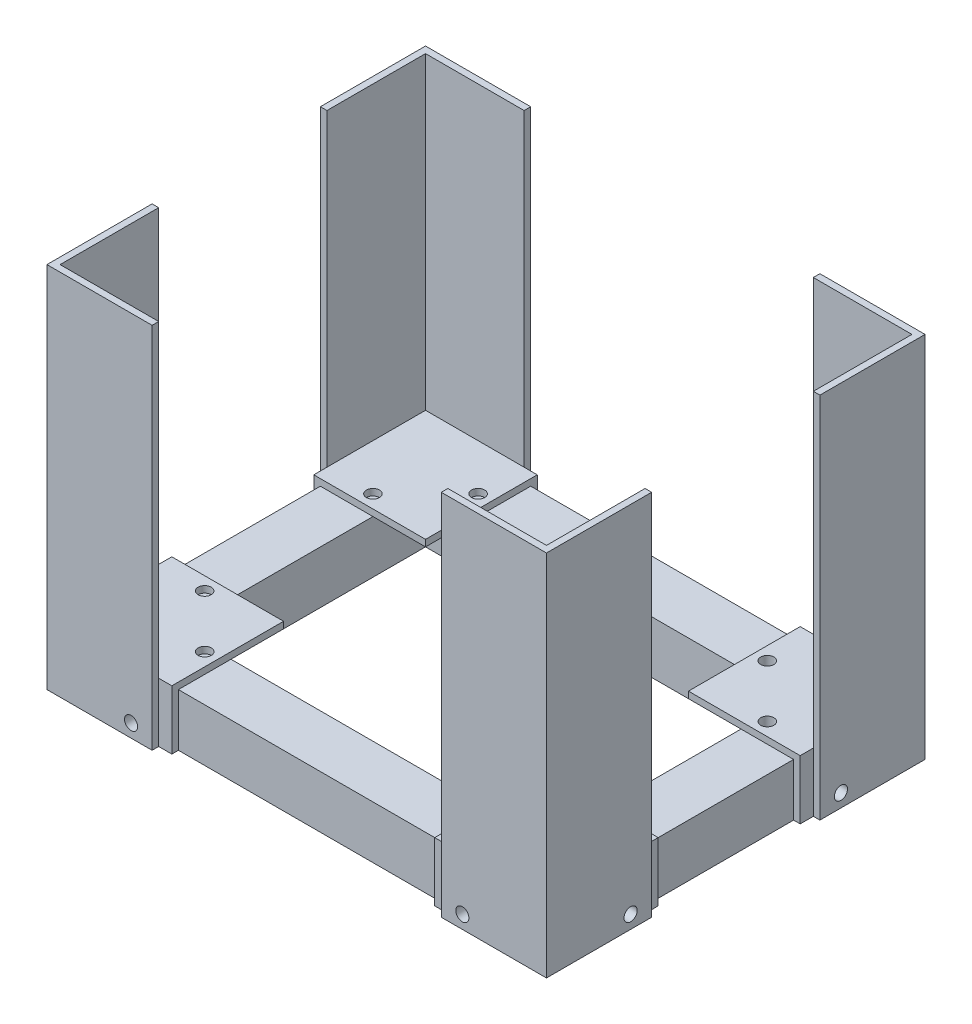
SolidWorks part; units mm, degrees
ref_plane "Front Plane" through (0, 0, 0) normal (0, 0, 1) x (1, 0, 0)
ref_plane "Top Plane" through (0, 0, 0) normal (0, 1, 0) x (1, 0, 0)
ref_plane "Right Plane" through (0, 0, 0) normal (1, 0, 0) x (0, 0, -1)
sketch "Sketch2" plane through (0, 0, 0) normal (0, 1, 0) x (1, 0, 0)
  line L0 (88.9, -59.69) -> (114.3, -59.69)
  line L1 (114.3, 85.09) -> (-114.3, 85.09)
  line L2 (114.3, 85.09) -> (114.3, -85.09)
  line L3 (114.3, -85.09) -> (-114.3, -85.09)
  line L4 (-114.3, 85.09) -> (-114.3, -85.09)
  line L5 (0, -85.09) -> (0, 85.09) construction
  line L6 (114.3, 0) -> (-114.3, 0) construction
  line L7 (-88.9, 59.69) -> (88.9, 59.69)
  line L8 (-88.9, 59.69) -> (-88.9, -59.69)
  line L9 (-88.9, -59.69) -> (88.9, -59.69)
  line L10 (88.9, 59.69) -> (88.9, -59.69)
  line L11 (0, -59.69) -> (0, 59.69) construction
  line L12 (-88.9, 0) -> (88.9, 0) construction
  line L13 (114.3, -59.69) -> (88.9, -59.69)
  line L14 (-114.3, -59.69) -> (-88.9, -59.69)
  line L17 (-88.9, 59.69) -> (-114.3, 59.69)
  line L18 (-114.3, 59.69) -> (-88.9, 59.69)
  line L19 (88.9, 59.69) -> (114.3, 59.69)
  line L20 (114.3, 59.69) -> (88.9, 59.69)
  point P0 (0, 0)
  point P4 (0, 0)
  dimension "D1" = 228.6
  dimension "D2" = 170.18
  dimension "D3" = 177.8
  dimension "D4" = 119.38
extrude "Boss-Extrude1" add sketch "Sketch2" along normal blind 25.4 contours L14 L4 L3 L2 L0 L9 | L19 L10 L0 L2 | L7 L19 L2 L1 L4 L17 | L8 L17 L4 L14 region at (101.6, 0, 0) region at (0, 0, 72.39) region at (-101.6, 0, 0) region at (0, 0, -72.39)
sketch "Sketch8" plane through (0, 25.4, 0) normal (0, 1, 0) x (1, 0, 0)
  line L1 (-114.3, -85.09) -> (-63.5, -85.09)
  line L2 (-114.3, -85.09) -> (-114.3, -88.265)
  line L3 (-114.3, -88.265) -> (-63.5, -88.265)
  line L4 (-63.5, -85.09) -> (-63.5, -88.265)
  line L5 (-114.3, -88.265) -> (-117.475, -88.265)
  line L6 (-114.3, -88.265) -> (-114.3, -34.29)
  line L7 (-114.3, -34.29) -> (-117.475, -34.29)
  line L8 (-117.475, -88.265) -> (-117.475, -34.29)
  dimension "D1" = 50.8
  dimension "D2" = 53.975
  dimension "D3" = 3.175
  dimension "D4" = 3.175
extrude "Boss-Extrude9" add sketch "Sketch8" against normal blind 25.4 contours L2 L1 L4 L3 | L6 L7 L8 L5
sketch "Sketch11" plane through (0, 25.4, 0) normal (0, 1, 0) x (1, 0, 0)
  line L0 (-117.475, -88.265) -> (-63.5, -88.265)
  line L1 (-117.475, -88.265) -> (-117.475, -34.29)
  line L2 (-63.5, -88.265) -> (-63.5, -34.29)
  line L3 (-117.475, -34.29) -> (-63.5, -34.29)
  point P0 (-196.4741, 4.7858)
extrude "Boss-Extrude12" add sketch "Sketch11" along normal blind 3.175
chamfer "Chamfer3" distance 5.08 angle 45 1 edges at (-117.475, 14.2875, 88.265)
sketch "Sketch10" plane through (0, 0, 0) normal (0, -1, 0) x (-1, 0, 0)
  line L0 (112.395, -88.265) -> (63.5, -88.265) construction
  line L1 (117.475, -83.185) -> (117.475, -34.29) construction
  line L2 (117.475, -40.64) -> (120.65, -40.64)
  line L3 (117.475, -40.64) -> (117.475, -88.265)
  line L4 (117.475, -88.265) -> (120.65, -88.265)
  line L5 (120.65, -40.64) -> (120.65, -88.265)
  line L7 (120.65, -88.265) -> (69.85, -88.265)
  line L8 (120.65, -88.265) -> (120.65, -91.44)
  line L9 (120.65, -91.44) -> (69.85, -91.44)
  line L10 (69.85, -88.265) -> (69.85, -91.44)
  point P4 (0, 0)
  point P5 (117.7066, -89.4721)
  point P10 (0, 0)
  point P12 (0, 0)
  point P13 (0, 0)
  point P14 (0, 0)
  point P15 (0, 0)
  point P16 (117.1952, -92.4558)
  dimension "D1" = 50.8
  dimension "D2" = 3.175
  dimension "D3" = 47.625
  dimension "D4" = 3.175
  dimension "D5" = 0
  dimension "D6" = 0
extrude "Boss-Extrude11" add sketch "Sketch10" against normal blind 177.8 contours L5 L2 L3 L4 | L8 L9 L10 L7
sketch "Sketch13" plane through (0, 0, 91.44) normal (0, 0, 1) x (1, 0, 0)
  line L0 (-69.85, 177.8) -> (-69.85, 0) construction
  line L1 (-120.65, 0) -> (-69.85, 0) construction
  circle A0 centre (-80.01, 6.35) radius 3.175
  dimension "D1" = 6.35
  dimension "D2" = 10.16
  dimension "D3" = 6.35
extrude "Cut-Extrude3" cut sketch "Sketch13" against normal blind 31.75
sketch "Sketch14" plane through (0, 28.575, 0) normal (0, 1, 0) x (1, 0, 0)
  line L1 (-63.5, -85.09) -> (-63.5, -59.69) construction
  line L2 (-63.5, -59.69) -> (88.9, -59.69) construction
  line L3 (-63.5, -34.29) -> (-117.475, -34.29) construction
  line L5 (-88.9, 59.69) -> (-88.9, -34.29) construction
  circle A0 centre (-69.85, -66.04) radius 3.175
  circle A1 centre (-95.25, -40.64) radius 3.175
  point P12 (-92.7177, -34.29)
  point P13 (-117.475, -38.1119)
  point P14 (0, 0)
  point P15 (0, 0)
  dimension "D1" = 6.35
  dimension "D3" = 6.35
  dimension "D4" = 6.35
  dimension "D2" = 6.35
  dimension "D5" = 6.35
  dimension "D6" = 6.35
extrude "Cut-Extrude4" cut sketch "Sketch14" against normal up to surface (28.575 mm away) up to face at (-61.9125, 0, 42.4392)
sketch "Sketch16" plane through (-120.65, 0, 0) normal (-1, 0, 0) x (0, 0, 1)
  line L0 (40.64, 0) -> (91.44, 0) construction
  line L1 (40.64, 177.8) -> (40.64, 0) construction
  circle A0 centre (50.8, 6.35) radius 3.175
  dimension "D1" = 6.35
  dimension "D2" = 6.35
  dimension "D3" = 10.16
extrude "Cut-Extrude5" cut sketch "Sketch16" against normal blind 31.75
mirror "Mirror70" about plane through (0, 0, 0) normal (0, 0, 1) of "Boss-Extrude1", "Boss-Extrude12", "Boss-Extrude11", "Boss-Extrude9", "Cut-Extrude3", "Cut-Extrude5", "Cut-Extrude4"
mirror "Mirror71" about plane through (0, 0, 0) normal (1, 0, 0) of "Mirror70", "Boss-Extrude1"
